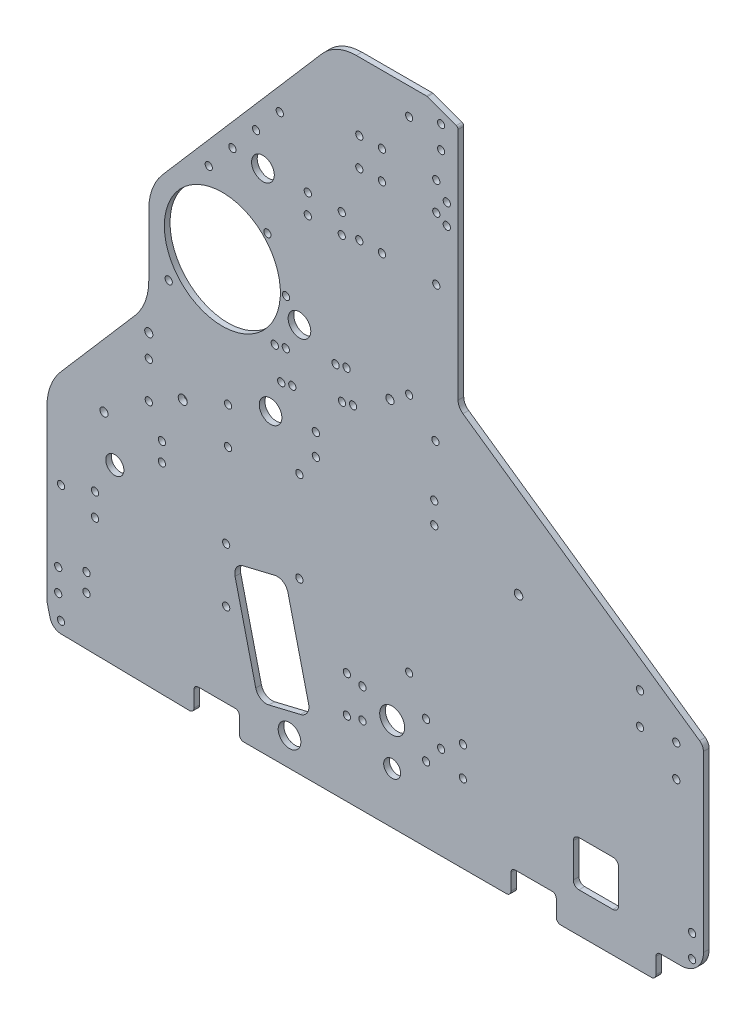
SolidWorks part; units mm, degrees
ref_plane "Front Plane" through (0, 0, 0) normal (0, 0, 1) x (1, 0, 0)
ref_plane "Top Plane" through (0, 0, 0) normal (0, 1, 0) x (1, 0, 0)
ref_plane "Right Plane" through (0, 0, 0) normal (1, 0, 0) x (0, 0, -1)
sketch "Sketch1" plane through (0, 0, 0) normal (0, 0, 1) x (1, 0, 0)
  line L0 (82.55, -20.32) -> (82.55, -6.35)
  line L2 (0, 0) -> (0, 157.48)
  line L4 (368.3, -20.32) -> (368.3, 106.68)
  line L5 (82.55, -6.35) -> (107.95, -6.35)
  line L6 (107.95, -6.35) -> (107.95, -20.32)
  line L7 (107.95, -20.32) -> (260.35, -20.32)
  line L8 (260.35, -20.32) -> (260.35, -6.35)
  line L9 (260.35, -6.35) -> (285.75, -6.35)
  line L10 (285.75, -6.35) -> (285.75, -20.32)
  line L11 (285.75, -20.32) -> (368.3, -20.32)
  line L12 (361.95, 12.7) -> (368.3, 12.7) construction
  line L13 (0, 0) -> (6.35, 0) construction
  line L14 (0.1896, -7.8901) -> (1.7771, -14.2401)
  line L15 (7.8295, -19.0491) -> (82.55, -20.32)
  line L16 (0, 0) -> (0, -6.35)
  line L17 (76.2, 128.905) -> (79.375, 128.905) construction
  line L18 (57.15, 118.5863) -> (101.6, 118.5862) construction
  line L19 (57.15, 118.5863) -> (57.15, 139.2238) construction
  line L20 (101.6, 118.5862) -> (101.6, 139.2237) construction
  line L21 (57.15, 139.2238) -> (101.6, 139.2237) construction
  line L22 (57.15, 118.5863) -> (101.6, 139.2237) construction
  line L23 (101.6, 118.5862) -> (57.15, 139.2238) construction
  line L24 (101.6, 139.2237) -> (125.4682, 147.9111) construction
  line L25 (203.2, 59.805) -> (203.2, 194.805) construction
  line L26 (203.2, 194.805) -> (203.2, 329.805) construction
  line L27 (355.6, 332.105) -> (330.2, 332.105) construction
  line L28 (330.2, 332.105) -> (330.2, 217.805) construction
  line L29 (330.2, 217.805) -> (355.6, 217.805) construction
  line L30 (355.6, 217.805) -> (355.6, 332.105) construction
  line L31 (203.2, 344.805) -> (203.2, 194.805) construction
  line L32 (50.8, 332.105) -> (76.2, 332.105) construction
  line L33 (76.2, 332.105) -> (76.2, 217.805) construction
  line L34 (50.8, 217.805) -> (50.8, 332.105) construction
  line L35 (76.2, 217.805) -> (50.8, 217.805) construction
  line L36 (213.2, 344.805) -> (230.6638, 338.455)
  line L37 (203.2, 344.805) -> (161.925, 344.805)
  line L38 (203.2, 344.805) -> (213.2, 344.805)
  line L39 (348.5362, 344.805) -> (413.4623, 344.805)
  line L40 (348.5362, 344.805) -> (230.6638, 344.805) construction
  line L42 (161.925, 344.805) -> (0, 157.48)
  line L44 (230.6638, 338.455) -> (230.6638, 202.565)
  line L45 (230.6638, 202.565) -> (368.3, 106.68)
  line L46 (213.2, 344.805) -> (-141.0713, 344.805) construction
  circle A0 centre (6.35, 0) radius 2.032
  circle A1 centre (6.35, 12.7) radius 2.032
  circle A2 centre (361.95, 0) radius 2.032
  circle A3 centre (361.95, 12.7) radius 2.032
  arc A5 (1.7771, -14.2401) -> (7.8295, -19.0491) centre (7.9375, -12.7) ccw
  circle A6 centre (7.9375, -12.7) radius 2.032
  arc A7 (0, -6.35) -> (0.1896, -7.8901) centre (6.35, -6.35) ccw
  circle A8 centre (38.1, 78.105) radius 5.08
  circle A9 centre (76.2, 128.905) radius 2.54
  circle A10 centre (101.6, 118.5862) radius 2.032
  circle A11 centre (101.6, 139.2237) radius 2.032
  circle A12 centre (57.15, 139.2238) radius 2.032
  circle A13 centre (57.15, 118.5863) radius 2.032
  circle A15 centre (203.2, 59.805) radius 2
  circle A16 centre (203.2, 194.805) radius 2
  circle A17 centre (203.2, 329.805) radius 2
  circle A18 centre (63.5, 313.055) radius 2.032
  circle A20 centre (355.6, 332.105) radius 2.032
  circle A21 centre (330.2, 332.105) radius 2.032
  circle A22 centre (355.6, 217.805) radius 2.032
  circle A23 centre (330.2, 217.805) radius 2.032
  circle A24 centre (50.8, 332.105) radius 2.032
  circle A25 centre (76.2, 332.105) radius 2.032
  circle A26 centre (50.8, 217.805) radius 2.032
  circle A27 centre (76.2, 217.805) radius 2.032
  circle A28 centre (221.1381, 335.28) radius 2
  circle A29 centre (224.3138, 298.831) radius 2.032
  circle A30 centre (353.06, 100.7351) radius 2.032
  circle A31 centre (332.74, 115.9751) radius 2.032
  circle A32 centre (332.74, 98.1951) radius 2.032
  circle A33 centre (353.06, 82.9551) radius 2.032
  circle A34 centre (117.3562, 280.4276) radius 2.032
  circle A35 centre (104.0678, 265.0548) radius 2.032
  circle A36 centre (90.7795, 249.682) radius 2.032
  circle A38 centre (130.6445, 295.8004) radius 2.032
  circle A39 centre (68.326, 182.9237) radius 2.032
  circle A40 centre (224.3138, 287.401) radius 2.032
  circle A41 centre (125.4682, 147.9111) radius 6.35
  circle A42 centre (221.1381, 322.58) radius 2
  point P82 (203.2, 344.805)
  point P90 (368.3, 62.484)
  dimension "D6" = 4.064
  dimension "D10" = 6.35
  dimension "D11" = 4.064
  dimension "D17" = 38.1
  dimension "D27" = 4
  dimension "D31" = 4.064
  dimension "D32" = 41.275
  dimension "D36" = 4.064
  dimension "D47" = 39.624
  dimension "D48" = 4.064
  dimension "D25" = 5.08
  dimension "D26" = 4.064
  dimension "D52" = 4.064
  dimension "D65" = 4.064
  dimension "D69" = 10.16
  dimension "D72" = 12.7
  dimension "D2" = 127
  dimension "D3" = 13.97
  dimension "D4" = 25.4
  dimension "D5" = 152.4
  dimension "D7" = 12.7
  dimension "D8" = 6.35
  dimension "D9" = 20.32
  dimension "D12" = 12.7
  dimension "D13" = 1.5875
  dimension "D14" = 82.55
  dimension "D15" = 368.3
  dimension "D16" = 6.35
  dimension "D18" = 98.425
  dimension "D19" = 38.1
  dimension "D20" = 50.8
  dimension "D21" = 3.175
  dimension "D22" = 270
  dimension "D23" = 20.6375
  dimension "D24" = 44.45
  dimension "D28" = 135
  dimension "D29" = 12.7
  dimension "D30" = 15
  dimension "D33" = 63.5
  dimension "D34" = 27.4638
  dimension "D35" = 12.7
  dimension "D37" = 114.3
  dimension "D38" = 25.4
  dimension "D39" = 12.7
  dimension "D40" = 157.48
  dimension "D41" = 142.24
  dimension "D42" = 365.125
  dimension "D43" = 10
  dimension "D44" = 6.35
  dimension "D45" = 31.75
  dimension "D46" = 3.175
  dimension "D49" = 6.35
  dimension "D50" = 203.2
  dimension "D51" = 15.24
  dimension "D53" = 17.78
  dimension "D54" = 17.78
  dimension "D55" = 20.32
  dimension "D56" = 15.24
  dimension "D57" = 92.202
  dimension "D58" = 8.382
  dimension "D59" = 20.32
  dimension "D60" = 20.32
  dimension "D61" = 8.382
  dimension "D62" = 20.32
  dimension "D63" = 8.382
  dimension "D64" = 8.382
  dimension "D66" = 35.052
  dimension "D67" = 68.326
  dimension "D68" = 11.43
  dimension "D70" = 25.4
  dimension "D71" = 110
  dimension "D73" = 17.9381
  dimension "D74" = 12.7
extrude "Boss-Extrude1" add sketch "Sketch1" along normal blind 3.175 contours L16 A7 L14 A5 L15 L2 A0 A1 A6 region at (171.5045, 119.4976, 0)
fillet "Fillet1" radius 2.286 4 edges at (285.75, -6.35, 1.5875) (107.95, -6.35, 1.5875) (260.35, -6.35, 1.5875) (82.55, -6.35, 1.5875)
fillet "Fillet2" radius 6.35 1 edges at (230.6638, 202.565, 1.5875)
sketch "Sketch2" plane through (0, 0, 0) normal (0, 0, -1) x (-1, 0, 0)
  circle A0 centre (-100.5528, 71.086) radius 2.032 construction
  circle A1 centre (-100.5528, 40.606) radius 2.032 construction
  circle A2 centre (-22.225, 18.2025) radius 2.032 construction
  circle A3 centre (-22.225, 8.0425) radius 2.032 construction
  circle A4 centre (-100.5528, 71.086) radius 2.032
  circle A5 centre (-100.5528, 40.606) radius 2.032
  circle A6 centre (-22.225, 18.2025) radius 2.032
  circle A7 centre (-22.225, 8.0425) radius 2.032
extrude "Cut-Extrude1" cut sketch "Sketch2" against normal through all
fillet "Fillet3" radius 1.5875 2 edges at (230.6638, 338.455, 1.5875) (213.2, 344.805, 1.5875)
sketch "Sketch3" plane through (0, 0, 3.175) normal (0, 0, 1) x (1, 0, 0)
  line L0 (132.9524, 63.2646) -> (132.7215, 64.2281) construction
  line L1 (128.3814, 66.8897) -> (110.6828, 62.6472) construction
  line L2 (114.5132, 58.4237) -> (126.8822, 61.3887) construction
  line L3 (108.0212, 58.3071) -> (108.2522, 57.3436) construction
  line L4 (131.2006, 57.703) -> (140.0164, 20.9265) construction
  line L5 (144.0993, 16.7636) -> (132.9524, 63.2646) construction
  line L6 (108.2522, 57.3436) -> (119.3991, 10.8426) construction
  line L7 (121.1509, 16.4042) -> (112.3351, 53.1807) construction
  line L8 (119.3991, 10.8426) -> (119.6301, 9.8791) construction
  line L9 (144.3303, 15.8001) -> (144.0993, 16.7636) construction
  line L10 (137.8383, 15.6835) -> (125.4694, 12.7185) construction
  line L11 (123.9701, 7.2175) -> (141.6687, 11.4601) construction
  line L12 (132.9524, 63.2646) -> (132.7215, 64.2281)
  line L13 (128.3814, 66.8897) -> (110.6828, 62.6472)
  line L14 (114.5132, 58.4237) -> (126.8822, 61.3887)
  line L15 (108.0212, 58.3071) -> (108.2522, 57.3436)
  line L16 (131.2006, 57.703) -> (140.0164, 20.9265)
  line L17 (144.0993, 16.7636) -> (132.9524, 63.2646)
  line L18 (108.2522, 57.3436) -> (119.3991, 10.8426)
  line L19 (121.1509, 16.4042) -> (112.3351, 53.1807)
  line L20 (119.3991, 10.8426) -> (119.6301, 9.8791)
  line L21 (144.3303, 15.8001) -> (144.0993, 16.7636)
  line L22 (137.8383, 15.6835) -> (125.4694, 12.7185)
  line L23 (123.9701, 7.2175) -> (141.6687, 11.4601)
  line L24 (127.7894, 69.3598) -> (110.0908, 65.1172)
  line L25 (105.5512, 57.715) -> (105.7822, 56.7515)
  line L26 (105.7822, 56.7515) -> (116.9291, 10.2505)
  line L27 (116.9291, 10.2505) -> (117.16, 9.287)
  line L28 (124.5622, 4.7475) -> (142.2608, 8.99)
  line L29 (146.8003, 16.3922) -> (146.5694, 17.3557)
  line L30 (146.5694, 17.3557) -> (135.4225, 63.8567)
  line L31 (135.4225, 63.8567) -> (135.1915, 64.8202)
  line L32 (14.605, -0.1369) -> (103.7278, 32.3011) construction
  line L33 (14.605, -0.1369) -> (103.7278, 32.3011)
  line L34 (0, -6.35) -> (0, 157.48) construction
  line L35 (-39.6666, 74.7152) -> (103.7278, 126.9065) construction
  line L36 (26.9875, 46.9531) -> (26.9875, 59.6531) construction
  line L37 (107.95, -20.32) -> (260.35, -20.32) construction
  line L38 (64.5259, 92.5258) -> (64.5259, 102.9405) construction
  line L39 (131.6538, 14.201) -> (136.0946, -4.3242) construction
  arc A0 (132.7215, 64.2281) -> (128.6308, 66.9403) centre (129.2206, 63.3889) ccw construction
  arc A1 (110.6828, 62.6472) -> (110.4377, 62.5791) centre (111.522, 59.1463) ccw construction
  arc A2 (128.6308, 66.9403) -> (128.3814, 66.8897) centre (129.2206, 63.3889) ccw construction
  arc A3 (110.4377, 62.5791) -> (108.0212, 58.3071) centre (111.522, 59.1463) ccw construction
  arc A4 (119.6301, 9.8791) -> (123.7207, 7.1669) centre (123.1309, 10.7183) ccw construction
  arc A5 (141.9139, 11.5281) -> (144.3303, 15.8001) centre (140.8295, 14.9609) ccw construction
  arc A6 (141.6687, 11.4601) -> (141.9139, 11.5281) centre (140.8295, 14.9609) ccw construction
  arc A7 (123.7207, 7.1669) -> (123.9701, 7.2175) centre (123.1309, 10.7183) ccw construction
  arc A8 (132.7215, 64.2281) -> (128.6308, 66.9403) centre (129.2206, 63.3889) ccw
  arc A9 (110.6828, 62.6472) -> (110.4377, 62.5791) centre (111.522, 59.1463) ccw
  arc A10 (128.6308, 66.9403) -> (128.3814, 66.8897) centre (129.2206, 63.3889) ccw
  arc A11 (110.4377, 62.5791) -> (108.0212, 58.3071) centre (111.522, 59.1463) ccw
  arc A12 (119.6301, 9.8791) -> (123.7207, 7.1669) centre (123.1309, 10.7183) ccw
  arc A13 (141.9139, 11.5281) -> (144.3303, 15.8001) centre (140.8295, 14.9609) ccw
  arc A14 (141.6687, 11.4601) -> (141.9139, 11.5281) centre (140.8295, 14.9609) ccw
  arc A15 (123.7207, 7.1669) -> (123.9701, 7.2175) centre (123.1309, 10.7183) ccw
  arc A16 (110.0908, 65.1172) -> (109.6726, 65.0012) centre (111.522, 59.1463) ccw
  arc A17 (109.6726, 65.0012) -> (105.5512, 57.715) centre (111.522, 59.1463) ccw
  arc A18 (117.16, 9.287) -> (124.1369, 4.6613) centre (123.1309, 10.7183) ccw
  arc A19 (124.1369, 4.6613) -> (124.5622, 4.7475) centre (123.1309, 10.7183) ccw
  arc A20 (142.2608, 8.99) -> (142.6789, 9.1061) centre (140.8295, 14.9609) ccw
  arc A21 (142.6789, 9.1061) -> (146.8003, 16.3922) centre (140.8295, 14.9609) ccw
  arc A22 (135.1915, 64.8202) -> (128.2147, 69.446) centre (129.2206, 63.3889) ccw
  arc A23 (128.2147, 69.446) -> (127.7894, 69.3598) centre (129.2206, 63.3889) ccw
  circle A24 centre (136.0946, -4.3242) radius 6.35
  circle A26 centre (134.1437, 208.2281) radius 2.032 construction
  circle A33 centre (26.9875, 46.9531) radius 2.032
  circle A34 centre (26.9875, 59.6531) radius 2.032
  circle A35 centre (7.9375, 53.3031) radius 2.032
  circle A37 centre (32.0306, 100.8109) radius 32.385 construction
  circle A38 centre (32.0306, 100.8109) radius 2.286
  circle A39 centre (123.682, 233.4851) radius 2.032 construction
  circle A40 centre (64.5259, 102.9405) radius 2.032
  circle A41 centre (64.5259, 92.5258) radius 2.032
  circle A42 centre (134.1437, 208.2281) radius 2.032
  circle A43 centre (123.682, 233.4851) radius 2.032
  ellipse E0 centre (124.5974, 48.8487) end of major axis (128.5376, 61.3578) minor radius 6 (131.2006, 57.703) -> (126.8822, 61.3887) ccw construction
  ellipse E1 centre (122.2349, 48.2824) end of major axis (113.0518, 57.6456) minor radius 6 (114.5132, 58.4237) -> (112.3351, 53.1807) ccw construction
  ellipse E2 centre (127.7541, 25.2585) end of major axis (131.6942, 37.7675) minor radius 6 (121.1509, 16.4042) -> (125.4694, 12.7185) ccw construction
  ellipse E3 centre (130.1166, 25.8248) end of major axis (139.2998, 16.4616) minor radius 6 (137.8383, 15.6835) -> (140.0164, 20.9265) ccw construction
  ellipse E4 centre (124.5974, 48.8487) end of major axis (120.6573, 36.3397) minor radius 6 (131.2006, 57.703) -> (126.8822, 61.3887) ccw
  ellipse E5 centre (122.2349, 48.2824) end of major axis (131.4181, 38.9192) minor radius 6 (114.5132, 58.4237) -> (112.3351, 53.1807) ccw
  ellipse E6 centre (127.7541, 25.2585) end of major axis (131.6942, 37.7675) minor radius 6 (121.1509, 16.4042) -> (125.4694, 12.7185) ccw
  ellipse E7 centre (130.1166, 25.8248) end of major axis (139.2998, 16.4616) minor radius 6 (137.8383, 15.6835) -> (140.0164, 20.9265) ccw
  point P93 (26.9875, 53.3031)
  point P115 (32.0306, 100.8109)
  dimension "D3" = 64.77
  dimension "D4" = 4.572
  dimension "D8" = 4.064
  dimension "D13" = 12.7
  dimension "D2" = 88.9
  dimension "D5" = 7.9375
  dimension "D6" = 19.05
  dimension "D7" = 73.6231
  dimension "D9" = 12.7
  dimension "D10" = 10.4147
  dimension "D11" = 37.5384
  dimension "D12" = 45.5727
  dimension "D14" = 19.05
  dimension "D1" = 2.54
extrude "Cut-Extrude2" cut sketch "Sketch3" against normal through all contours A22 A23 L24 A16 A17 L25 L26 L27 A18 A19 L28 A20 A21 L29 L30 L31 A15 A12 L20 L18 L15 A11 A9 L13 A10 A8 L12 L17 L21 A13 A14 L23 | A12 A15 L23 A14 A13 L21 L17 L12 A8 A10 L13 A9 A11 L15 L18 L20 E7 L22 E6 L19 E5 L14 E4 L16 | L22 E7 L16 E4 L14 E5 L19 E6 | A38 | A41 | A40 | A35 | A34 | A33 | A43 | A42 | A24 region at (137.844, 39.8506, 3.175) region at (126.1758, 37.0536, 3.175) region at (128.1544, 68.6507, 3.175) region at (32.0306, 100.8109, 3.175) region at (64.5259, 102.9405, 3.175) region at (64.5259, 92.5258, 3.175)
sketch "Sketch4" plane through (0, 0, 3.175) normal (0, 0, 1) x (1, 0, 0)
  line L0 (57.15, 139.2238) -> (101.6, 139.2237) construction
  line L1 (168.275, 21.4312) -> (212.725, 21.4312) construction
  line L2 (168.275, 21.4312) -> (168.275, 42.0687) construction
  line L3 (168.275, 42.0687) -> (212.725, 42.0687) construction
  line L4 (212.725, 21.4312) -> (212.725, 42.0687) construction
  line L5 (168.275, 21.4312) -> (212.725, 42.0687) construction
  line L6 (168.275, 42.0687) -> (212.725, 21.4312) construction
  line L7 (57.15, 118.5863) -> (57.15, 139.2238) construction
  line L8 (107.95, -20.32) -> (260.35, -20.32) construction
  line L9 (193.675, 31.75) -> (177.005, 31.75) construction
  line L10 (190.5, 31.75) -> (193.675, 31.75) construction
  line L11 (6.35, 12.7) -> (361.95, 12.7) construction
  line L12 (107.95, -6.35) -> (107.95, -20.32) construction
  line L13 (193.675, 31.75) -> (220.6625, 31.75) construction
  line L14 (177.005, 23.4569) -> (177.005, 40.0431) construction
  line L15 (213.2, 44.805) -> (193.2, 44.805) construction
  line L16 (213.2, 44.805) -> (213.2, 344.805) construction
  line L17 (213.2, 344.805) -> (193.2, 344.805) construction
  line L18 (193.2, 44.805) -> (193.2, 344.805) construction
  line L19 (213.2, 44.805) -> (193.2, 344.805) construction
  line L20 (213.2, 344.805) -> (193.2, 44.805) construction
  line L21 (226.1381, 335.28) -> (226.1381, 31.75) construction
  line L22 (237.33, 40.0431) -> (233.3612, 40.0431) construction
  line L23 (237.33, 23.4569) -> (233.3612, 23.4569) construction
  circle A0 centre (168.275, 42.0687) radius 2.032
  circle A1 centre (212.725, 42.0687) radius 2.032
  circle A2 centre (212.725, 21.4312) radius 2.032
  circle A3 centre (168.275, 21.4312) radius 2.032
  circle A4 centre (193.675, 31.75) radius 6.985
  circle A7 centre (220.6625, 31.75) radius 14.2875 construction
  circle A8 centre (193.675, 31.75) radius 12.7 construction
  circle A9 centre (177.005, 40.0431) radius 2.032
  circle A10 centre (177.005, 23.4569) radius 2.032
  circle A11 centre (237.33, 40.0431) radius 2.032 construction
  circle A12 centre (237.33, 23.4569) radius 2.032 construction
  circle A13 centre (193.675, 8.4667) radius 4.7625
  circle A14 centre (221.1381, 31.75) radius 2.032
  circle A15 centre (221.1381, 31.75) radius 5 construction
  circle A16 centre (221.1381, 335.28) radius 5 construction
  circle A17 centre (233.3612, 23.4569) radius 2.032
  circle A18 centre (233.3612, 40.0431) radius 2.032
  point P0 (190.5, 31.75)
  point P26 (203.2, 194.805)
  point P38 (177.005, 31.75)
  dimension "D1" = 4.064
  dimension "D4" = 13.97
  dimension "D7" = 9.525
  dimension "D10" = 25.4
  dimension "D11" = 28.575
  dimension "D16" = 10
  dimension "D17" = 4.064
  dimension "D18" = 10
  dimension "D2" = 52.07
  dimension "D3" = 3.175
  dimension "D5" = 82.55
  dimension "D6" = 26.9875
  dimension "D8" = 20
  dimension "D9" = 300
  dimension "D12" = 16.67
  dimension "D13" = 16.5862
  dimension "D14" = 60.325
  dimension "D15" = 23.2833
  dimension "D19" = 3.9688
extrude "Cut-Extrude3" cut sketch "Sketch4" against normal through all
sketch "Sketch5" plane through (0, 0, 0) normal (0, 0, -1) x (-1, 0, 0)
  line L0 (-57.15, 223.5947) -> (-57.15, 165.3337)
  line L1 (-161.925, 344.805) -> (-52.7201, 218.4699) construction
  line L2 (-57.15, 165.3337) -> (0, 99.219)
  line L3 (0, -6.35) -> (0, 157.48) construction
  line L4 (-147.864, -30.311) -> (-147.864, -16.0874)
  line L5 (-50.4199, 215.8089) -> (0, 157.48) construction
  line L6 (-57.15, 223.5947) -> (0, 157.48)
  line L7 (0, 157.48) -> (0, 99.219)
  line L8 (-98.425, 208.2281) -> (-141.6756, 197.9719) construction
  line L10 (-341.63, -6.35) -> (-341.63, -21.2964)
  line L12 (-371.0782, -6.35) -> (-341.63, -6.35)
  line L13 (-285.75, -20.32) -> (-368.3, -20.32) construction
  line L14 (-371.0782, -6.35) -> (-371.0782, -21.2964)
  line L15 (-371.0782, -21.2964) -> (-341.63, -21.2964)
  circle A0 centre (-98.425, 208.2281) radius 32.5437
  circle A1 centre (-141.6756, 197.9719) radius 6.35
  circle A3 centre (-264.5736, 128.3328) radius 2.39
  dimension "D3" = 65.0875
  dimension "D7" = 12.7
  dimension "D8" = 4.78
  dimension "D1" = 38.1
  dimension "D2" = 57.15
  dimension "D4" = 41.275
  dimension "D5" = 41.275
  dimension "D6" = 13.97
  dimension "D9" = 22.2382
  dimension "D10" = 117.7733
  dimension "D11" = 11.6447
  dimension "D12" = 123.5853
  dimension "D14" = 62.5
  dimension "D13" = 44.45
extrude "Cut-Extrude5" cut sketch "Sketch5" against normal through all contours A0 | L7 L6 L0 L2 | A3 | L14 L15 L10 L12 | A1 region at (28.575, 161.4068, 0) region at (356.3541, -13.8232, 0) region at (98.425, 208.2281, 0) region at (264.5736, 128.3328, 0)
fillet "Fillet4" radius 31.75 3 edges at (0, 99.219, 1.5875) (57.15, 165.3337, 1.5875) (57.15, 223.5947, 1.5875)
sketch "Sketch6" plane through (0, 0, 3.175) normal (0, 0, 1) x (1, 0, 0)
  line L0 (285.75, -20.32) -> (341.63, -20.32) construction
  line L1 (298.45, 27.305) -> (317.5, 27.305)
  line L2 (295.275, 24.13) -> (295.275, 5.08)
  line L3 (298.45, 1.905) -> (317.5, 1.905)
  line L4 (320.675, 24.13) -> (320.675, 5.08)
  line L5 (295.275, 27.305) -> (320.675, 1.905) construction
  line L6 (295.275, 1.905) -> (320.675, 27.305) construction
  line L7 (368.3, -6.35) -> (368.3, 106.68) construction
  arc A0 (295.275, 5.08) -> (298.45, 1.905) centre (298.45, 5.08) ccw
  arc A1 (317.5, 1.905) -> (320.675, 5.08) centre (317.5, 5.08) ccw
  arc A2 (317.5, 27.305) -> (320.675, 24.13) centre (317.5, 24.13) cw
  arc A3 (298.45, 27.305) -> (295.275, 24.13) centre (298.45, 24.13) ccw
  point P0 (307.975, 14.605)
  dimension "D2" = 3.175
  dimension "D1" = 25.4
  dimension "D3" = 22.225
  dimension "D4" = 47.625
extrude "Cut-Extrude6" cut sketch "Sketch6" against normal through all
fillet "Fillet5" radius 25.4 1 edges at (161.925, 344.805, 1.5875)
sketch "Sketch8" plane through (0, 0, 0) normal (0, 0, -1) x (-1, 0, 0)
  line L0 (-230.6638, 337.343) -> (-230.6638, 205.8802) construction
  line L1 (-230.6638, 255.905) -> (-175.26, 255.905) construction
  line L2 (-175.26, 255.905) -> (-175.26, 306.705) construction
  line L3 (-175.26, 306.705) -> (-230.6638, 306.705) construction
  line L4 (-173.5432, 344.805) -> (-212.9203, 344.805) construction
  line L7 (-107.95, -20.32) -> (-260.35, -20.32) construction
  circle A0 centre (-218.44, 290.83) radius 3.9687
  circle A1 centre (-218.44, 290.83) radius 2.032
  circle A2 centre (218.44, 265.7972) radius 3.9687
  circle A3 centre (218.44, 265.7972) radius 2.032
  circle A4 centre (-205.74, 290.83) radius 3.9687
  circle A5 centre (-205.74, 290.83) radius 2.032
  circle A6 centre (-187.96, 290.83) radius 3.9687
  circle A7 centre (-187.96, 290.83) radius 2.032
  circle A8 centre (-187.96, 306.705) radius 2.032
  circle A9 centre (-175.26, 290.83) radius 3.9687
  circle A10 centre (-175.26, 290.83) radius 2.032
  circle A11 centre (-205.74, 306.705) radius 2.032
  circle A13 centre (-205.74, 255.905) radius 2.032
  circle A14 centre (-187.96, 255.905) radius 2.032
  circle A16 centre (-218.44, 306.705) radius 2.032
  circle A17 centre (-175.26, 306.705) radius 2.032
  circle A18 centre (-175.26, 255.905) radius 2.032
  circle A19 centre (-218.44, 255.905) radius 2.032
  circle A20 centre (-218.44, 306.705) radius 3.9687
  circle A21 centre (-205.74, 306.705) radius 3.9687
  circle A22 centre (-175.26, 306.705) radius 3.9687
  circle A23 centre (-218.44, 255.905) radius 3.9687
  circle A24 centre (-205.74, 255.905) radius 3.9687
  circle A25 centre (-187.96, 255.905) radius 3.9687
  circle A26 centre (-175.26, 255.905) radius 3.9687
  circle A27 centre (-187.96, 306.705) radius 3.9687
  dimension "D1" = 7.9375
  dimension "D7" = 4.064
  dimension "D13" = 12.2237
  dimension "D2" = 12.2237
  dimension "D3" = 12.7
  dimension "D4" = 17.78
  dimension "D5" = 12.7
  dimension "D6" = 88.9
  dimension "D8" = 38.1
  dimension "D9" = 17.78
  dimension "D10" = 12.7
  dimension "D11" = 55.4037
  dimension "D12" = 12.7
  dimension "D14" = 311.15
extrude "Cut-Extrude7" cut sketch "Sketch8" against normal through all contours A16 | A17 | A18 | A19 | A8 | A14 | A1 | A7 | A10 region at (218.44, 306.705, 0) region at (175.26, 306.705, 0) region at (175.26, 255.905, 0) region at (218.44, 255.905, 0)
sketch "Sketch10" plane through (0, 0, 3.175) normal (0, 0, 1) x (1, 0, 0)
  circle A4 centre (141.6425, 74.6844) radius 2.032 construction
  circle A5 centre (141.6425, 125.4844) radius 2.032 construction
  circle A6 centre (141.6425, 74.6844) radius 2.032
  circle A7 centre (141.6425, 125.4844) radius 2.032
extrude "Cut-Extrude8" cut sketch "Sketch10" against normal through all
sketch "Sketch11" plane through (0, 0, 3.175) normal (0, 0, 1) x (1, 0, 0)
  ellipse E4 centre (150.8814, 138.43) end of major axis (150.8814, 140.462) minor radius 2.032
  ellipse E5 centre (150.8814, 150.495) end of major axis (150.8814, 152.527) minor radius 2.032
  ellipse E6 centre (217.3024, 150.495) end of major axis (217.3024, 152.527) minor radius 2.032
  ellipse E7 centre (217.3024, 138.43) end of major axis (217.3024, 140.462) minor radius 2.032
extrude "Cut-Extrude9" cut sketch "Sketch11" against normal through all
sketch "Sketch12" plane through (0, 0, 0) normal (0, 0, -1) x (-1, 0, 0)
  line L0 (-173.5432, 344.805) -> (-212.9203, 344.805) construction
  circle A0 centre (-165.4175, 264.635) radius 2.032
  circle A1 centre (-203.2, 329.805) radius 2 construction
  circle A2 centre (-165.4175, 253.5225) radius 2.032
  circle A3 centre (-146.3675, 253.5225) radius 2.032
  circle A4 centre (-146.3675, 264.635) radius 2.032
  dimension "D1" = 80.17
  dimension "D2" = 4.064
  dimension "D3" = 37.7825
  dimension "D4" = 11.1125
  dimension "D5" = 19.05
extrude "Cut-Extrude10" cut sketch "Sketch12" against normal through all
sketch "Sketch14" plane through (0, 0, 0) normal (0, 0, -1) x (-1, 0, 0)
  line L0 (-130.6445, 295.8004) -> (-121.1847, 263.6885) construction
  line L1 (-121.1847, 263.6885) -> (-90.7795, 249.682) construction
  line L2 (-154.3272, 336.0154) -> (-64.88, 232.5373) construction
  line L4 (-118.517, 269.4796) -> (-115.3937, 261.0208) construction
  line L5 (-118.517, 269.4796) -> (-126.9758, 266.3562) construction
  line L6 (-126.9758, 266.3562) -> (-123.8524, 257.8974) construction
  line L7 (-115.3937, 261.0208) -> (-123.8524, 257.8974) construction
  line L8 (-118.517, 269.4796) -> (-123.8524, 257.8974) construction
  line L9 (-126.9758, 266.3562) -> (-115.3937, 261.0208) construction
  circle A0 centre (-121.1847, 263.6885) radius 6.376
  dimension "D1" = 22.225
  dimension "D2" = 9.017
extrude "Cut-Extrude11" cut sketch "Sketch14" against normal through all
sketch "Sketch15" plane through (0, 0, 3.175) normal (0, 0, 1) x (1, 0, 0)
  line L1 (27.1508, 77.7471) -> (81.7263, 77.7471) construction
  line L2 (57.15, 139.2238) -> (57.15, 151.9238) construction
  line L3 (27.1508, 77.7471) -> (52.3291, 153.5255) construction
  line L4 (56.0505, 156.8833) -> (192.439, 187.1199) construction
  circle A0 centre (27.1508, 77.7471) radius 2.159 construction
  circle A1 centre (27.1508, 77.7471) radius 2.159 construction
  circle A2 centre (57.15, 139.2238) radius 2.032 construction
  circle A3 centre (57.15, 139.2238) radius 2.032 construction
  circle A4 centre (57.15, 151.9238) radius 2.286
  circle A5 centre (192.439, 187.1199) radius 2.286
  circle A6 centre (57.15, 151.9238) radius 5.08 construction
  arc A9 (163.8737, 173.6806) -> (164.5125, 170.7993) centre (165.557, 172.5423) ccw construction
  arc A10 (173.4398, 172.7784) -> (172.801, 175.6597) centre (171.7565, 173.9167) ccw construction
  arc A11 (172.801, 175.6597) -> (173.4398, 172.7784) centre (171.7565, 173.9167) ccw construction
  arc A12 (164.5125, 170.7993) -> (163.8737, 173.6806) centre (165.557, 172.5423) ccw construction
  arc A13 (169.1589, 192.0883) -> (169.7976, 189.2071) centre (168.1143, 190.3453) ccw construction
  arc A14 (169.7976, 189.2071) -> (169.1589, 192.0883) centre (168.1143, 190.3453) ccw construction
  arc A15 (160.2316, 190.1092) -> (160.8704, 187.2279) centre (161.9149, 188.9709) ccw construction
  arc A16 (160.8704, 187.2279) -> (160.2316, 190.1092) centre (161.9149, 188.9709) ccw construction
  arc A17 (129.7766, 166.1214) -> (130.4154, 163.2402) centre (131.4599, 164.9832) ccw construction
  arc A18 (139.3426, 165.2193) -> (138.7039, 168.1005) centre (137.6593, 166.3576) ccw construction
  arc A19 (138.7039, 168.1005) -> (139.3426, 165.2193) centre (137.6593, 166.3576) ccw construction
  arc A20 (130.4154, 163.2402) -> (129.7766, 166.1214) centre (131.4599, 164.9832) ccw construction
  arc A21 (135.7005, 181.6479) -> (135.0617, 184.5292) centre (134.0172, 182.7862) ccw construction
  arc A22 (135.0617, 184.5292) -> (135.7005, 181.6479) centre (134.0172, 182.7862) ccw construction
  arc A23 (126.1345, 182.55) -> (126.7732, 179.6688) centre (127.8177, 181.4118) ccw construction
  arc A24 (126.7732, 179.6688) -> (126.1345, 182.55) centre (127.8177, 181.4118) ccw construction
  arc A25 (163.8737, 173.6806) -> (164.5125, 170.7993) centre (165.557, 172.5423) ccw
  arc A26 (173.4398, 172.7784) -> (172.801, 175.6597) centre (171.7565, 173.9167) ccw
  arc A27 (172.801, 175.6597) -> (173.4398, 172.7784) centre (171.7565, 173.9167) ccw
  arc A28 (164.5125, 170.7993) -> (163.8737, 173.6806) centre (165.557, 172.5423) ccw
  arc A29 (169.1589, 192.0883) -> (169.7976, 189.2071) centre (168.1143, 190.3453) ccw
  arc A30 (169.7976, 189.2071) -> (169.1589, 192.0883) centre (168.1143, 190.3453) ccw
  arc A31 (160.2316, 190.1092) -> (160.8704, 187.2279) centre (161.9149, 188.9709) ccw
  arc A32 (160.8704, 187.2279) -> (160.2316, 190.1092) centre (161.9149, 188.9709) ccw
  arc A33 (129.7766, 166.1214) -> (130.4154, 163.2402) centre (131.4599, 164.9832) ccw
  arc A34 (139.3426, 165.2193) -> (138.7039, 168.1005) centre (137.6593, 166.3576) ccw
  arc A35 (138.7039, 168.1005) -> (139.3426, 165.2193) centre (137.6593, 166.3576) ccw
  arc A36 (130.4154, 163.2402) -> (129.7766, 166.1214) centre (131.4599, 164.9832) ccw
  arc A37 (135.7005, 181.6479) -> (135.0617, 184.5292) centre (134.0172, 182.7862) ccw
  arc A38 (135.0617, 184.5292) -> (135.7005, 181.6479) centre (134.0172, 182.7862) ccw
  arc A39 (126.1345, 182.55) -> (126.7732, 179.6688) centre (127.8177, 181.4118) ccw
  arc A40 (126.7732, 179.6688) -> (126.1345, 182.55) centre (127.8177, 181.4118) ccw
  dimension "D2" = 4.572
  dimension "D6" = 10.16
  dimension "D1" = 12.7
  dimension "D3" = 139.7
  dimension "D4" = 12.5
extrude "Cut-Extrude12" cut sketch "Sketch15" against normal through all
sketch "Sketch16" plane through (0, 0, 3.175) normal (0, 0, 1) x (1, 0, 0)
  circle A0 centre (98.425, 208.2281) radius 34.925 construction
  circle A1 centre (98.425, 208.2281) radius 34.925
  circle A2 centre (98.425, 208.2281) radius 36.195
  dimension "D1" = 1.27
fillet "Fillet6" radius 12.7 1 edges at (368.3, -6.35, 1.5875)
fillet "Fillet7" radius 5.08 1 edges at (368.3, 106.68, 1.5875)
fillet "Fillet8" radius 2.54 6 edges at (82.55, -20.32, 1.5875) (107.95, -20.32, 1.5875) (260.35, -20.32, 1.5875) (285.75, -20.32, 1.5875) (341.63, -20.32, 1.5875) (341.63, -6.35, 1.5875)
sketch "Sketch17" plane through (0, 0, 3.175) normal (0, 0, 1) x (1, 0, 0)
  line L0 (230.6638, 337.343) -> (230.6638, 205.8802) construction
  line L1 (173.5432, 344.805) -> (212.9203, 344.805) construction
  circle A0 centre (217.9638, 179.705) radius 2.032
  dimension "D1" = 12.7
  dimension "D3" = 4.064
  dimension "D2" = 165.1
extrude "Cut-Extrude13" cut sketch "Sketch17" against normal through all contours A0
